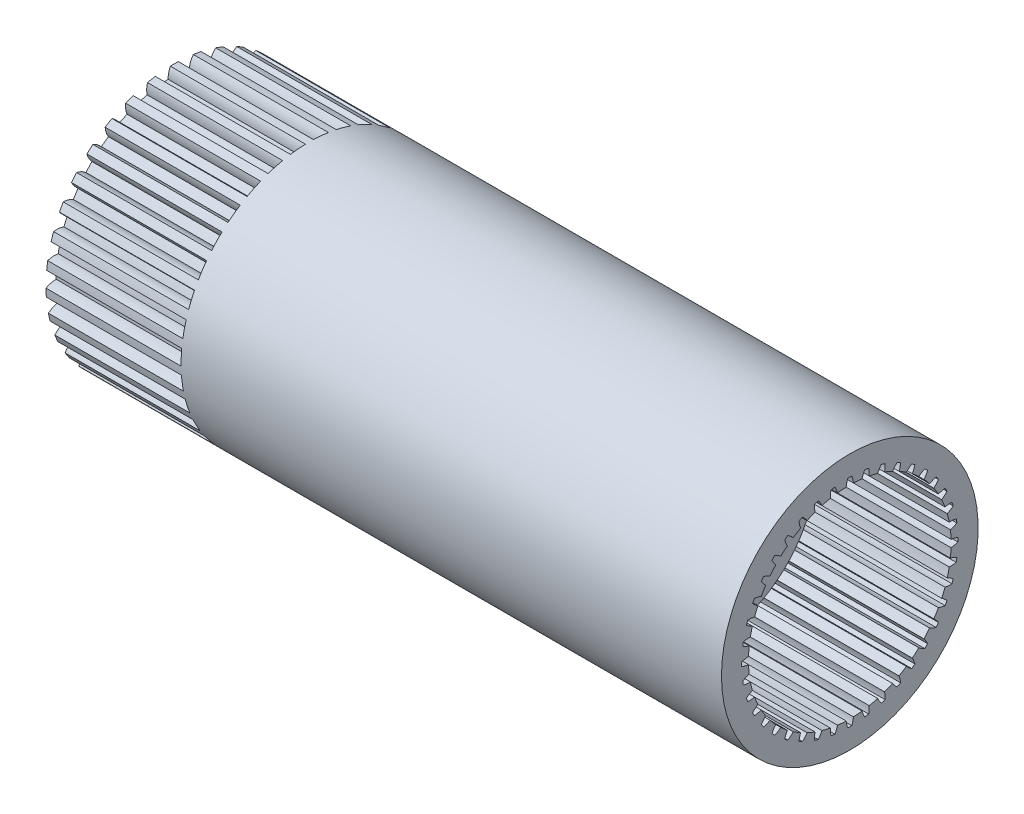
SolidWorks part; units mm, degrees
ref_plane "Front Plane" through (0, 0, 0) normal (0, 0, 1) x (1, 0, 0)
ref_plane "Top Plane" through (0, 0, 0) normal (0, 1, 0) x (1, 0, 0)
ref_plane "Right Plane" through (0, 0, 0) normal (1, 0, 0) x (0, 0, -1)
sketch "Sketch1" plane through (0, 0, 0) normal (0, 0, 1) x (1, 0, 0)
  line L0 (-50.4808, 0) -> (58.5577, 0) construction
  line L2 (-47.7885, 17.5) -> (52.2115, 17.5)
  line L3 (-47.7885, 17.5) -> (-47.7885, 0)
  line L4 (-47.7885, 0) -> (52.2115, 0)
  line L5 (52.2115, 17.5) -> (52.2115, 0)
  dimension "D1" = 17.5
  dimension "D2" = 100
revolve "Revolve1" add sketch "Sketch1" angle 360 about L0
sketch "Sketch2" plane through (-47.7885, 0, 0) normal (-1, 0, 0) x (0, 0, 1)
  line L0 (0, 0) -> (0, 4.1398) construction
  arc A0 (-0.9159, 17.476) -> (-2.2193, 17.3587) centre (0, 0) ccw
  arc A1 (0.5906, 18.9908) -> (-0.5906, 18.9908) centre (0, 0) ccw
  arc A2 (-0.9159, 17.476) -> (-0.5906, 18.9908) centre (2.2552, 17.5875) cw
  arc A3 (0.9159, 17.476) -> (0.5906, 18.9908) centre (-2.2552, 17.5875) ccw
  arc A4 (3.9721, 18.5802) -> (2.8098, 18.7911) centre (0, 0) ccw
  arc A5 (2.2193, 17.3587) -> (2.8098, 18.7911) centre (5.3593, 16.9022) cw
  arc A6 (2.2193, 17.3587) -> (0.9159, 17.476) centre (0, 0) ccw
  arc A7 (4.0216, 17.0316) -> (3.9721, 18.5802) centre (0.9214, 17.7075) ccw
  arc A8 (7.2259, 17.5723) -> (6.1199, 17.9874) centre (0, 0) ccw
  arc A9 (5.2832, 16.6835) -> (6.1199, 17.9874) centre (8.2912, 15.6736) cw
  arc A10 (5.2832, 16.6835) -> (0, 17.5) centre (0, 0) ccw
  arc A11 (6.9981, 16.0398) -> (7.2259, 17.5723) centre (4.0684, 17.2584) ccw
  arc A12 (10.2474, 15.9997) -> (9.2333, 16.6056) centre (0, 0) ccw
  arc A13 (8.1772, 15.472) -> (9.2333, 16.6056) centre (10.9566, 13.9413) cw
  arc A14 (8.1772, 15.472) -> (-5.2832, 16.6835) centre (0, 0) ccw
  arc A15 (9.7497, 14.5325) -> (10.2474, 15.9997) centre (7.0846, 16.2547) ccw
  arc A16 (12.9396, 13.9128) -> (12.05, 14.6901) centre (0, 0) ccw
  arc A17 (10.8084, 13.7633) -> (12.05, 14.6901) centre (13.2698, 11.7608) cw
  arc A18 (10.8084, 13.7633) -> (-5.2832, 16.6835) centre (0, 0) ccw
  arc A19 (12.1879, 12.5581) -> (12.9396, 13.9128) centre (9.8731, 14.7284) ccw
  arc A20 (15.2159, 11.3788) -> (14.4794, 12.3024) centre (0, 0) ccw
  arc A21 (13.0923, 11.6122) -> (14.4794, 12.3024) centre (15.1566, 9.2024) cw
  arc A22 (13.0923, 11.6122) -> (-5.2832, 16.6835) centre (0, 0) ccw
  arc A23 (14.2343, 10.1801) -> (15.2159, 11.3788) centre (12.3443, 12.7288) ccw
  arc A24 (17.0031, 8.479) -> (16.4433, 9.5193) centre (0, 0) ccw
  arc A25 (14.9553, 9.0879) -> (16.4433, 9.5193) centre (16.5561, 6.3482) cw
  arc A26 (14.9553, 9.0879) -> (15.8233, 7.4748) centre (0, 0) ccw
  arc A27 (15.8233, 7.4748) -> (17.0031, 8.479) centre (14.4188, 10.3201) ccw
  arc A28 (18.2439, 5.3067) -> (17.8788, 6.4302) centre (0, 0) ccw
  arc A29 (16.3377, 6.2714) -> (17.8788, 6.4302) centre (17.4236, 3.29) cw
  arc A30 (16.3377, 6.2714) -> (16.9037, 4.5293) centre (0, 0) ccw
  arc A31 (16.9037, 4.5293) -> (18.2439, 5.3067) centre (16.0298, 7.5797) ccw
  arc A32 (18.8982, 1.9639) -> (18.7397, 3.1345) centre (0, 0) ccw
  arc A33 (17.1949, 3.2535) -> (18.7397, 3.1345) centre (17.731, 0.126) cw
  arc A34 (17.1949, 3.2535) -> (17.4408, 1.4383) centre (0, 0) ccw
  arc A35 (17.4408, 1.4383) -> (18.8982, 1.9639) centre (17.1256, 4.5956) ccw
  arc A36 (18.9452, -1.4421) -> (18.9982, -0.262) centre (0, 0) ccw
  arc A37 (17.4995, 0.1309) -> (18.9982, -0.262) centre (17.4686, -3.042) cw
  arc A38 (17.4995, 0.1309) -> (17.4173, -1.699) centre (0, 0) ccw
  arc A39 (17.4173, -1.699) -> (18.9452, -1.4421) centre (17.671, 1.4639) ccw
  arc A40 (18.3832, -4.8017) -> (18.6461, -3.65) centre (0, 0) ccw
  arc A41 (17.2417, -2.9959) -> (18.6461, -3.65) centre (16.6447, -6.1123) cw
  arc A42 (17.2417, -2.9959) -> (16.8341, -4.7817) centre (0, 0) ccw
  arc A43 (16.8341, -4.7817) -> (18.3832, -4.8017) centre (17.6484, -1.7149) ccw
  arc A44 (17.2304, -8.007) -> (17.6947, -6.9207) centre (0, 0) ccw
  arc A45 (16.4296, -6.0263) -> (17.6947, -6.9207) centre (15.2858, -8.9861) cw
  arc A46 (16.4296, -6.0263) -> (15.7097, -7.7107) centre (0, 0) ccw
  arc A47 (15.7097, -7.7107) -> (17.2304, -8.007) centre (17.0585, -4.8386) ccw
  arc A48 (15.5238, -10.9549) -> (16.1746, -9.969) centre (0, 0) ccw
  arc A49 (15.0896, -8.8631) -> (16.1746, -9.969) centre (13.4357, -11.571) cw
  arc A50 (15.0896, -8.8631) -> (14.0805, -10.3919) centre (0, 0) ccw
  arc A51 (14.0805, -10.3919) -> (15.5238, -10.9549) centre (15.9204, -7.8067) ccw
  arc A52 (13.3183, -13.5508) -> (14.1346, -12.6969) centre (0, 0) ccw
  arc A53 (13.2645, -11.415) -> (14.1346, -12.6969) centre (11.1536, -13.7841) cw
  arc A54 (13.2645, -11.415) -> (11.9986, -12.739) centre (0, 0) ccw
  arc A55 (11.9986, -12.739) -> (13.3183, -13.5508) centre (14.2706, -10.524) ccw
  arc A56 (10.6847, -15.7111) -> (11.6404, -15.0167) centre (0, 0) ccw
  arc A57 (11.0131, -13.6001) -> (11.6404, -15.0167) centre (8.5132, -15.5542) cw
  arc A58 (11.0131, -13.6001) -> (9.5312, -14.6767) centre (0, 0) ccw
  arc A59 (9.5312, -14.6767) -> (10.6847, -15.7111) centre (12.1622, -12.903) ccw
  arc A60 (7.7076, -17.3664) -> (8.772, -16.8539) centre (0, 0) ccw
  arc A61 (8.4077, -15.348) -> (8.772, -16.8539) centre (5.599, -16.8243) cw
  arc A62 (8.4077, -15.348) -> (6.7574, -16.1427) centre (0, 0) ccw
  arc A63 (6.7574, -16.1427) -> (7.7076, -17.3664) centre (9.6628, -14.8673) ccw
  arc A64 (4.4829, -18.4636) -> (5.6216, -18.1493) centre (0, 0) ccw
  arc A65 (5.5321, -16.6026) -> (5.6216, -18.1493) centre (2.505, -17.5537) cw
  arc A66 (5.5321, -16.6026) -> (3.7664, -17.0899) centre (0, 0) ccw
  arc A67 (3.7664, -17.0899) -> (4.4829, -18.4636) centre (6.8529, -16.3537) ccw
  arc A68 (1.1141, -18.9673) -> (2.2906, -18.8614) centre (0, 0) ccw
  arc A69 (2.4787, -17.3236) -> (2.2906, -18.8614) centre (-0.6696, -17.7188) cw
  arc A70 (2.4787, -17.3236) -> (0.6543, -17.4878) centre (0, 0) ccw
  arc A71 (0.6543, -17.4878) -> (1.1141, -18.9673) centre (3.8227, -17.3145) ccw
  arc A72 (-2.2906, -18.8614) -> (-1.1141, -18.9673) centre (0, 0) ccw
  arc A73 (-0.6543, -17.4878) -> (-1.1141, -18.9673) centre (-3.8227, -17.3145) cw
  arc A74 (-0.6543, -17.4878) -> (-2.4787, -17.3236) centre (0, 0) ccw
  arc A75 (-2.4787, -17.3236) -> (-2.2906, -18.8614) centre (0.6696, -17.7188) ccw
  arc A76 (-5.6216, -18.1493) -> (-4.4829, -18.4636) centre (0, 0) ccw
  arc A77 (-3.7664, -17.0899) -> (-4.4829, -18.4636) centre (-6.8529, -16.3537) cw
  arc A78 (-3.7664, -17.0899) -> (-5.5321, -16.6026) centre (0, 0) ccw
  arc A79 (-5.5321, -16.6026) -> (-5.6216, -18.1493) centre (-2.505, -17.5537) ccw
  arc A80 (-8.772, -16.8539) -> (-7.7076, -17.3664) centre (0, 0) ccw
  arc A81 (-6.7574, -16.1427) -> (-7.7076, -17.3664) centre (-9.6628, -14.8673) cw
  arc A82 (-6.7574, -16.1427) -> (-8.4077, -15.348) centre (0, 0) ccw
  arc A83 (-8.4077, -15.348) -> (-8.772, -16.8539) centre (-5.599, -16.8243) ccw
  arc A84 (-11.6404, -15.0167) -> (-10.6847, -15.7111) centre (0, 0) ccw
  arc A85 (-9.5312, -14.6767) -> (-10.6847, -15.7111) centre (-12.1622, -12.903) cw
  arc A86 (-9.5312, -14.6767) -> (-11.0131, -13.6001) centre (0, 0) ccw
  arc A87 (-11.0131, -13.6001) -> (-11.6404, -15.0167) centre (-8.5132, -15.5542) ccw
  arc A88 (-14.1346, -12.6969) -> (-13.3183, -13.5508) centre (0, 0) ccw
  arc A89 (-11.9986, -12.739) -> (-13.3183, -13.5508) centre (-14.2706, -10.524) cw
  arc A90 (-11.9986, -12.739) -> (-13.2645, -11.415) centre (0, 0) ccw
  arc A91 (-13.2645, -11.415) -> (-14.1346, -12.6969) centre (-11.1536, -13.7841) ccw
  arc A92 (-16.1746, -9.969) -> (-15.5238, -10.9549) centre (0, 0) ccw
  arc A93 (-14.0805, -10.3919) -> (-15.5238, -10.9549) centre (-15.9204, -7.8067) cw
  arc A94 (-14.0805, -10.3919) -> (-15.0896, -8.8631) centre (0, 0) ccw
  arc A95 (-15.0896, -8.8631) -> (-16.1746, -9.969) centre (-13.4357, -11.571) ccw
  arc A96 (-17.6947, -6.9207) -> (-17.2304, -8.007) centre (0, 0) ccw
  arc A97 (-15.7097, -7.7107) -> (-17.2304, -8.007) centre (-17.0585, -4.8386) cw
  arc A98 (-15.7097, -7.7107) -> (-16.4296, -6.0263) centre (0, 0) ccw
  arc A99 (-16.4296, -6.0263) -> (-17.6947, -6.9207) centre (-15.2858, -8.9861) ccw
  arc A100 (-18.6461, -3.65) -> (-18.3832, -4.8017) centre (0, 0) ccw
  arc A101 (-16.8341, -4.7817) -> (-18.3832, -4.8017) centre (-17.6484, -1.7149) cw
  arc A102 (-16.8341, -4.7817) -> (-17.2417, -2.9959) centre (0, 0) ccw
  arc A103 (-17.2417, -2.9959) -> (-18.6461, -3.65) centre (-16.6447, -6.1123) ccw
  arc A104 (-18.9982, -0.262) -> (-18.9452, -1.4421) centre (0, 0) ccw
  arc A105 (-17.4173, -1.699) -> (-18.9452, -1.4421) centre (-17.671, 1.4639) cw
  arc A106 (-17.4173, -1.699) -> (-17.4995, 0.1309) centre (0, 0) ccw
  arc A107 (-17.4995, 0.1309) -> (-18.9982, -0.262) centre (-17.4686, -3.042) ccw
  arc A108 (-18.7397, 3.1345) -> (-18.8982, 1.9639) centre (0, 0) ccw
  arc A109 (-17.4408, 1.4383) -> (-18.8982, 1.9639) centre (-17.1256, 4.5956) cw
  arc A110 (-17.4408, 1.4383) -> (-17.1949, 3.2535) centre (0, 0) ccw
  arc A111 (-17.1949, 3.2535) -> (-18.7397, 3.1345) centre (-17.731, 0.126) ccw
  arc A112 (-17.8788, 6.4302) -> (-18.2439, 5.3067) centre (0, 0) ccw
  arc A113 (-16.9037, 4.5293) -> (-18.2439, 5.3067) centre (-16.0298, 7.5797) cw
  arc A114 (-16.9037, 4.5293) -> (-16.3377, 6.2714) centre (0, 0) ccw
  arc A115 (-16.3377, 6.2714) -> (-17.8788, 6.4302) centre (-17.4236, 3.29) ccw
  arc A116 (-16.4433, 9.5193) -> (-17.0031, 8.479) centre (0, 0) ccw
  arc A117 (-15.8233, 7.4748) -> (-17.0031, 8.479) centre (-14.4188, 10.3201) cw
  arc A118 (-15.8233, 7.4748) -> (-14.9553, 9.0879) centre (0, 0) ccw
  arc A119 (-14.9553, 9.0879) -> (-16.4433, 9.5193) centre (-16.5561, 6.3482) ccw
  arc A120 (-14.4794, 12.3024) -> (-15.2159, 11.3788) centre (0, 0) ccw
  arc A121 (-14.2343, 10.1801) -> (-15.2159, 11.3788) centre (-12.3443, 12.7288) cw
  arc A122 (-14.2343, 10.1801) -> (-13.0923, 11.6122) centre (0, 0) ccw
  arc A123 (-13.0923, 11.6122) -> (-14.4794, 12.3024) centre (-15.1566, 9.2024) ccw
  arc A124 (-12.05, 14.6901) -> (-12.9396, 13.9128) centre (0, 0) ccw
  arc A125 (-12.1879, 12.5581) -> (-12.9396, 13.9128) centre (-9.8731, 14.7284) cw
  arc A126 (-12.1879, 12.5581) -> (-10.8084, 13.7633) centre (0, 0) ccw
  arc A127 (-10.8084, 13.7633) -> (-12.05, 14.6901) centre (-13.2698, 11.7608) ccw
  arc A128 (-9.2333, 16.6056) -> (-10.2474, 15.9997) centre (0, 0) ccw
  arc A129 (-9.7497, 14.5325) -> (-10.2474, 15.9997) centre (-7.0846, 16.2547) cw
  arc A130 (-9.7497, 14.5325) -> (-8.1772, 15.472) centre (0, 0) ccw
  arc A131 (-8.1772, 15.472) -> (-9.2333, 16.6056) centre (-10.9566, 13.9413) ccw
  arc A132 (-6.1199, 17.9874) -> (-7.2259, 17.5723) centre (0, 0) ccw
  arc A133 (-6.9981, 16.0398) -> (-7.2259, 17.5723) centre (-4.0684, 17.2584) cw
  arc A134 (-6.9981, 16.0398) -> (-5.2832, 16.6835) centre (0, 0) ccw
  arc A135 (-5.2832, 16.6835) -> (-6.1199, 17.9874) centre (-8.2912, 15.6736) ccw
  arc A136 (-2.8098, 18.7911) -> (-3.9721, 18.5802) centre (0, 0) ccw
  arc A137 (-4.0216, 17.0316) -> (-3.9721, 18.5802) centre (-0.9214, 17.7075) cw
  arc A138 (-4.0216, 17.0316) -> (-2.2193, 17.3587) centre (0, 0) ccw
  arc A139 (-2.2193, 17.3587) -> (-2.8098, 18.7911) centre (-5.3593, 16.9022) ccw
  arc A140 (0, 17.5) -> (4.0216, 17.0316) centre (0, 0) ccw
  arc A141 (-0.9159, 17.476) -> (6.9981, 16.0398) centre (0, 0) ccw
  arc A142 (-4.0216, 17.0316) -> (0.9159, 17.476) centre (0, 0) ccw
  arc A143 (-6.9981, 16.0398) -> (9.7497, 14.5325) centre (0, 0) ccw
  arc A144 (-6.9981, 16.0398) -> (12.1879, 12.5581) centre (0, 0) ccw
  arc A145 (-6.9981, 16.0398) -> (14.2343, 10.1801) centre (0, 0) ccw
  point P213 (-27.4634, -15.7797)
  dimension "D1" = 38
extrude "Boss-Extrude1" add sketch "Sketch2" against normal blind 20 contours A122 A127 A124 A125 region at (-47.7885, 13.7019, -11.971)
pattern_circular "CirPattern1" count 35 over 360 about axis through (-47.7885, 0, 0) along (-1, 0, 0) of "Boss-Extrude1"
sketch "Sketch3" plane through (-47.7885, 0, 0) normal (-1, 0, 0) x (0, 0, 1)
  circle A0 centre (0, 0) radius 19
extrude "Boss-Extrude2" add sketch "Sketch3" against normal up to surface (100 mm away) from offset 20 up to face at (52.2115, 0, 17.5) offset against normal yes
sketch "Sketch4" plane through (52.2115, 0, 0) normal (1, 0, 0) x (0, 0, -1)
  line L0 (0, 0) -> (0, 24.2077) construction
  circle A0 centre (0, 0) radius 16
  circle A1 centre (0, 0) radius 15
  arc A2 (-0.5365, 14.9904) -> (-0.2939, 15.9973) centre (3.3766, 14.5803) cw
  arc A3 (0.5365, 14.9904) -> (0.2939, 15.9973) centre (-3.3766, 14.5803) ccw
  dimension "D1" = 32
  dimension "D2" = 30
extrude "Cut-Extrude1" cut sketch "Sketch4" against normal blind 20 contours A1 region at (52.2115, 0, 0)
extrude "Cut-Extrude2" cut sketch "Sketch4<3>" against normal blind 35 contours L0 A1 A3 A0 | A1 L0 A0 A2 region at (52.2115, 15.4518, 0.2251) region at (52.2115, 15.4518, -0.2251)
sketch "Sketch4<3>" plane through (52.2115, 0, 0) normal (1, 0, 0) x (0, 0, -1) same geometry as "Sketch4"
pattern_circular "CirPattern2" count 40 over 360 about axis through (52.2115, 0, 0) along (1, 0, 0) of "Cut-Extrude2"
